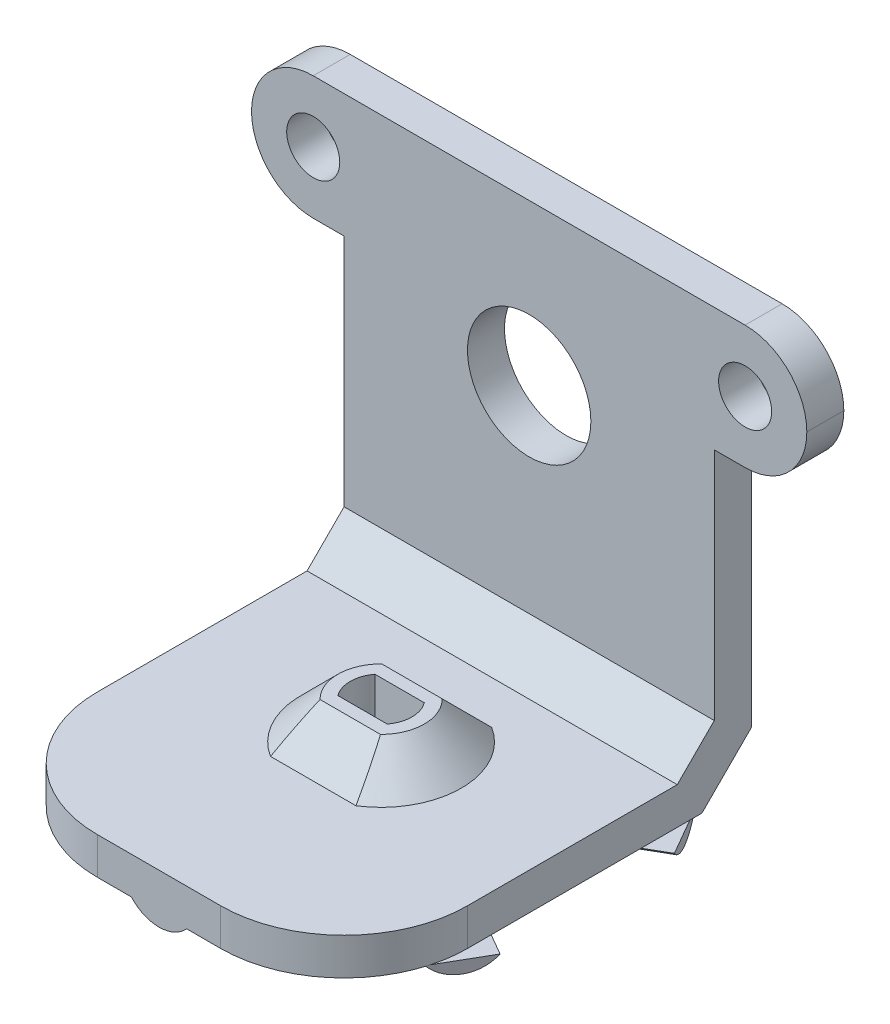
SolidWorks part; units mm, degrees
ref_plane "Front Plane" through (0, 0, 0) normal (0, 0, 1) x (1, 0, 0)
ref_plane "Top Plane" through (0, 0, 0) normal (0, 1, 0) x (1, 0, 0)
ref_plane "Right Plane" through (0, 0, 0) normal (1, 0, 0) x (0, 0, -1)
sketch "Sketch1" plane through (0, 0, 0) normal (0, 0, 1) x (1, 0, 0)
  line L0 (0, 0) -> (-17.5, 0) construction
  line L1 (0, 0) -> (0, -12.5) construction
  line L2 (0, -12.5) -> (0, -8) construction
  line L3 (-22.5, -30) -> (22.5, -30)
  line L4 (-22.5, -30) -> (-22.5, 5)
  line L5 (-22.5, 5) -> (22.5, 5)
  line L6 (22.5, -30) -> (22.5, 5)
  line L7 (-22.5, -30) -> (22.5, 5) construction
  line L8 (-22.5, 5) -> (22.5, -30) construction
  circle A0 centre (-17.5, 0) radius 2.15
  circle A1 centre (17.5, 0) radius 2.15
  circle A2 centre (0, -8) radius 5
  dimension "D1" = 4.3
  dimension "D5" = 10
  dimension "D2" = 35
  dimension "D3" = 5
  dimension "D6" = 8
  dimension "D7" = 35
  dimension "D4" = 5
extrude "Boss-Extrude1" add sketch "Sketch1" along normal blind 3
sketch "Sketch3" plane through (0, 0, 0) normal (-1, 0, 0) x (0, 0, 1)
  line L0 (3, -30) -> (33, -30)
  dimension "D1" = 30
extrude "Extrude-Thin1" add sketch "Sketch3" against normal mid plane 30 thin thin type one direction reverse wall 3
sketch "Sketch4" plane through (0, -27, 0) normal (0, 1, 0) x (1, 0, 0)
  line L0 (0, 0) -> (0, -15) construction
  line L1 (22.5, 0) -> (-22.5, 0) construction
  line L2 (-2, -13.5) -> (2, -13.5)
  line L3 (-2, -16.5) -> (2, -16.5)
  line L4 (0, -15) -> (-2.5, -15) construction
  arc A0 (-2, -13.5) -> (-2, -16.5) centre (0, -15) ccw
  arc A1 (0, -12.5) -> (-2, -13.5) centre (0, -15) ccw construction
  arc A2 (2, -13.5) -> (0, -12.5) centre (0, -15) ccw construction
  arc A3 (2, -16.5) -> (2, -13.5) centre (0, -15) ccw
  arc A4 (-2, -16.5) -> (2, -16.5) centre (0, -15) ccw construction
  dimension "D1" = 3
  dimension "D2" = 5
  dimension "D3" = 15
extrude "Cut-Extrude1" cut sketch "Sketch4" against normal through all
sketch "Sketch5" plane through (0, 0, 3) normal (0, 0, 1) x (1, 0, 0)
  line L0 (22.5, 5) -> (-22.5, 5) construction
  line L1 (-22.5, -30) -> (-15, -30)
  line L2 (-22.5, -30) -> (-22.5, -5)
  line L3 (-22.5, -5) -> (-15, -5)
  line L4 (-15, -30) -> (-15, -5)
  line L5 (-15, -27) -> (-15, -30) construction
  line L6 (0, 0) -> (0, -30) construction
  line L7 (15, -30) -> (-15, -30) construction
  line L8 (15, -30) -> (15, -5)
  line L9 (22.5, -5) -> (15, -5)
  line L10 (22.5, -30) -> (22.5, -5)
  line L11 (22.5, -30) -> (15, -30)
  dimension "D1" = 10
extrude "Cut-Extrude2" cut sketch "Sketch5" against normal through all both and the other way through all
sketch "Sketch6" plane through (0, -27, 0) normal (0, 1, 0) x (1, 0, 0)
  line L0 (-2, -16.5) -> (2, -16.5) construction
  line L1 (2, -13.5) -> (-2, -13.5) construction
  line L2 (-2, -16.5) -> (2, -16.5)
  line L3 (2, -13.5) -> (-2, -13.5)
  arc A0 (2, -16.5) -> (2, -13.5) centre (0, -15) ccw construction
  arc A1 (-2, -13.5) -> (-2, -16.5) centre (0, -15) ccw construction
  arc A2 (2, -16.5) -> (2, -13.5) centre (0, -15) ccw
  arc A3 (-2, -13.5) -> (-2, -16.5) centre (0, -15) ccw
extrude "Extrude-Thin2" add sketch "Sketch6" along normal blind 3 thin thin type one direction wall 1
chamfer "Chamfer1" distance 3 angle 45 4 edges at (0, -27, 12.5) (-3.5, -27, 15) (3.5, -27, 15) (0, -27, 17.5)
sketch "Sketch8" plane through (0, 0, 33) normal (0, 0, -1) x (-1, 0, 0)
  line L1 (0, -28) -> (0, 0) construction
  line L2 (15, -30) -> (-15, -30) construction
  line L3 (0, -30) -> (0, -31) construction
  line L4 (-2.2361, -30) -> (2.2361, -30)
  arc A0 (-2.2361, -30) -> (2.2361, -30) centre (0, -28) ccw
  dimension "D1" = 1
  dimension "D2" = 3
extrude "Boss-Extrude3" add sketch "Sketch8" along normal blind 8
pattern_circular "CirPattern1" count 6 over 360 of "Boss-Extrude3"
chamfer "Chamfer4" distance 3 angle 45 1 edges at (0, -30, 0)
fillet "Fillet1" radius 10 2 edges at (15, -28.5, 33) (-15, -28.5, 33)
chamfer "Chamfer2" distance 4 angle 45 2 edges at (8.618, -30, 0) (-8.618, -30, 0)
chamfer "Chamfer3" distance 3 angle 45 1 edges at (0, -27, 3)
fillet "Fillet2" radius 5 4 edges at (22.5, 5, 1.5) (22.5, -5, 1.5) (-22.5, -5, 1.5) (-22.5, 5, 1.5)
sketch "Sketch7" plane through (0, -30, 0) normal (0, -1, 0) x (1, 0, 0)
  line L0 (0, 15) -> (0, 2.5) construction
  line L1 (-10, 22.5) -> (10, 22.5) construction
  circle A0 centre (0, 2.5) radius 2
  circle A2 centre (0, 15) radius 12.5 construction
  circle A3 centre (-10, 22.5) radius 2
  circle A4 centre (10, 22.5) radius 2
  arc A5 (-2, 16.5) -> (-2, 13.5) centre (0, 15) ccw construction
  point P8 (0, 0)
  dimension "D1" = 25
  dimension "D3" = 4
  dimension "D2" = 20
equation "\"D4@Sketch1\"=\"D3@Sketch1\""
